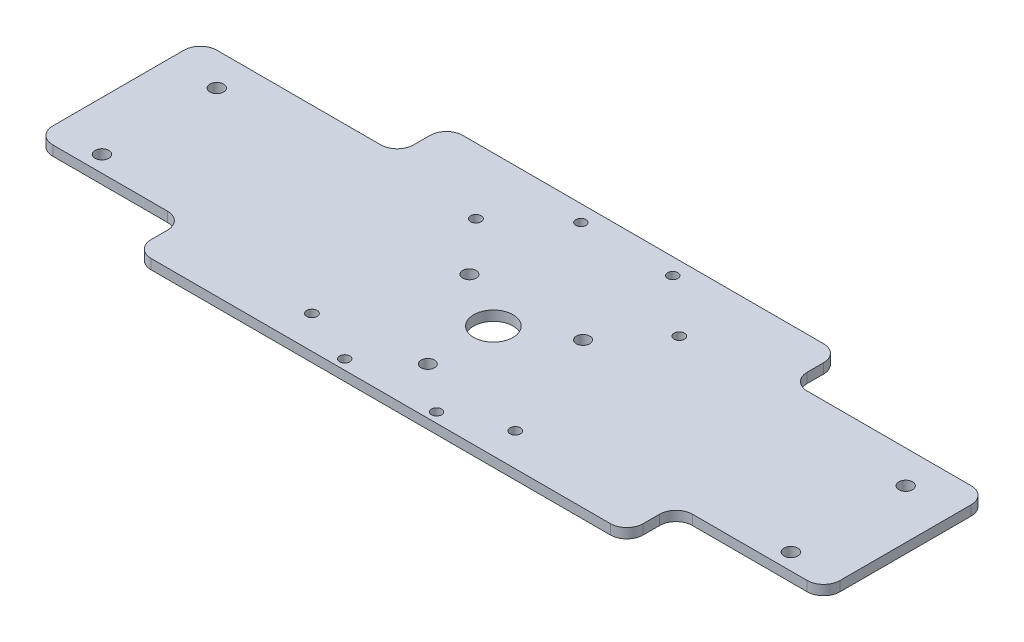
SolidWorks part; units mm, degrees
material "Thornel Mat VMA"
ref_plane "前视基准面" through (0, 0, 0) normal (0, 0, 1) x (1, 0, 0)
ref_plane "上视基准面" through (0, 0, 0) normal (0, 1, 0) x (1, 0, 0)
ref_plane "右视基准面" through (0, 0, 0) normal (1, 0, 0) x (0, 0, -1)
sketch "草图1" plane through (0, 0, 0) normal (0, 1, 0) x (1, 0, 0)
  line L0 (15, 65) -> (15, 0) construction
  line L1 (0, 0) -> (240, 0)
  line L2 (0, 0) -> (0, 65)
  line L3 (0, 65) -> (240, 65)
  line L4 (240, 0) -> (240, 65)
  line L5 (120, 65) -> (120, 0) construction
  line L6 (60, 65) -> (60, 80)
  line L7 (60, 80) -> (180, 80)
  line L8 (120, 65) -> (120, 80) construction
  line L9 (180, 65) -> (180, 80)
  circle A1 centre (15, 55) radius 2.1
  circle A2 centre (225, 20) radius 2.1
  circle A3 centre (15, 20) radius 2.1
  circle A4 centre (225, 55) radius 2.1
  dimension "D4" = 10
  dimension "D5" = 15
  dimension "D6" = 35
  dimension "D2" = 20
  dimension "D8" = 15
  dimension "D1" = 240
  dimension "D3" = 15
  dimension "D7" = 60
extrude "凸台-拉伸1" add sketch "草图1" along normal blind 3 contours L1 L4 L3 L2 A2 A1 A3 A4 | L3 L9 L7 L6 region at (120, 0, -32.4822) region at (120, 0, -72.5)
sketch "草图3" plane through (0, 0, 0) normal (0, -1, 0) x (1, 0, 0)
  line L0 (120, -80) -> (120, 0) construction
  line L1 (60, -80) -> (180, -80) construction
  line L2 (0, 0) -> (240, 0) construction
  line L3 (45, 0) -> (45, -15)
  line L4 (106, -3) -> (134, -3) construction
  line L5 (106, -3) -> (106, -75) construction
  line L6 (89, -35) -> (151, -35) construction
  line L7 (151, -60) -> (89, -60) construction
  line L8 (151, -60) -> (151, -10) construction
  line L9 (151, -10) -> (89, -10) construction
  line L10 (89, -60) -> (89, -10) construction
  line L11 (151, -60) -> (89, -10) construction
  line L12 (151, -10) -> (89, -60) construction
  line L13 (106, -75) -> (134, -75) construction
  line L14 (134, -3) -> (134, -75) construction
  line L15 (120, -75) -> (120, -3) construction
  line L16 (106, -39) -> (134, -39) construction
  line L17 (45, -15) -> (0, -15)
  line L18 (0, 0) -> (0, -65) construction
  line L19 (0, -15) -> (0, 0)
  line L20 (0, 0) -> (45, 0)
  line L21 (240, -15) -> (240, 0)
  line L22 (240, 0) -> (195, 0)
  line L23 (195, -15) -> (240, -15)
  line L24 (195, 0) -> (195, -15)
  circle A0 centre (89, -10) radius 1.6
  circle A1 centre (151, -10) radius 1.6
  circle A2 centre (151, -60) radius 1.6
  circle A3 centre (89, -60) radius 1.6
  circle A4 centre (106, -3) radius 1.55
  circle A5 centre (134, -3) radius 1.55
  circle A6 centre (134, -75) radius 1.55
  circle A7 centre (106, -75) radius 1.55
  point P12 (120, -35)
  point P489 (120, -39)
  dimension "D3" = 10
  dimension "D7" = 45
  dimension "D1" = 62
  dimension "D2" = 50
  dimension "D4" = 28
  dimension "D5" = 72
  dimension "D6" = 5
  dimension "D8" = 15
extrude "切除-拉伸2" cut sketch "草图3" against normal through all
fillet "圆角1" radius 5 12 edges at (195, 1.5, 0) (195, 1.5, -15) (240, 1.5, -15) (240, 1.5, -65) (180, 1.5, -65) (180, 1.5, -80) (60, 1.5, -80) (0, 1.5, -65) (60, 1.5, -65) (45, 1.5, -15) (45, 1.5, 0) (0, 1.5, -15)
sketch "草图4" plane through (0, 0, 0) normal (0, -1, 0) x (1, 0, 0)
  line L0 (65, -80) -> (175, -80) construction
  line L1 (65, -80) -> (175, -80) construction
  line L2 (120, -80) -> (120, 0) construction
  line L3 (50, 0) -> (190, 0) construction
  circle A0 centre (120, -34.3335) radius 6
  circle A1 centre (120, -14.3335) radius 2.05
  circle A2 centre (137.3205, -44.3335) radius 2.05
  circle A3 centre (102.6795, -44.3335) radius 2.05
  point P17 (120, -34.3335)
  dimension "D1" = 12
  dimension "D2" = 4.1
  dimension "D3" = 20
  dimension "D4" = 3
extrude "切除-拉伸3" cut sketch "草图4" against normal blind 10
